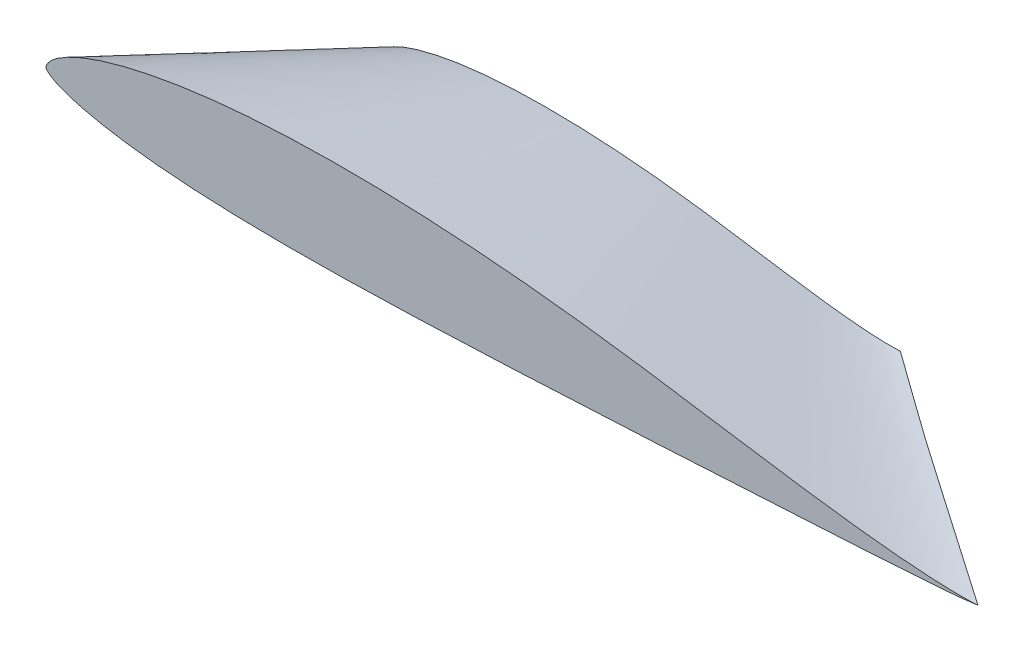
SolidWorks part; units mm, degrees
ref_plane "Front Plane" through (0, 0, 0) normal (0, 0, 1) x (1, 0, 0)
ref_plane "Top Plane" through (0, 0, 0) normal (0, 1, 0) x (1, 0, 0)
ref_plane "Right Plane" through (0, 0, 0) normal (1, 0, 0) x (0, 0, -1)
curve "Curve1"
  spline degree 3 poles (178.8235, -0.1536, 0) (180.3162, 0.0326, 0) (178.6769, -0.0979, 0) (177.3268, -0.1109, 0) (173.9976, -0.1057, 0) (169.9397, 0.1046, 0) (164.6882, 0.4858, 0) (158.5901, 1.1026, 0) (151.6988, 1.9482, 0) (144.1808, 2.9934, 0) (136.1635, 4.1927, 0) (127.7797, 5.4908, 0) (119.1442, 6.8173, 0) (110.3463, 8.0754, 0) (101.4587, 9.2, 0) (92.5465, 10.1562, 0) (83.6758, 10.9156, 0) (74.9166, 11.4682, 0) (66.342, 11.806, 0) (58.028, 11.9274, 0) (50.0487, 11.8319, 0) (42.4741, 11.515, 0) (35.367, 10.9819, 0) (28.7822, 10.24, 0) (22.7701, 9.3088, 0) (17.3773, 8.2269, 0) (12.6499, 7.0268, 0) (8.6305, 5.74, 0) (5.3502, 4.4039, 0) (2.8359, 3.0632, 0) (1.2518, 1.9009, 0) (0.4818, 1.0554, 0) (0.1891, 0.6046, 0) (0.0579, 0.3158, 0) (-0.0016, 0.0856, 0) (-0.0042, -0.0985, 0) (0.0738, -0.2696, 0) (0.2282, -0.4702, 0) (0.4808, -0.7088, 0) (0.9335, -1.0446, 0) (2.0075, -1.6855, 0) (4.0408, -2.5002, 0) (7.1529, -3.4084, 0) (11.097, -4.2605, 0) (15.8307, -5.0186, 0) (21.3187, -5.6503, 0) (27.5191, -6.1332, 0) (34.3853, -6.4628, 0) (41.8623, -6.6344, 0) (49.8874, -6.6565, 0) (58.3886, -6.5391, 0) (67.2847, -6.306, 0) (76.4836, -5.9763, 0) (85.8843, -5.5795, 0) (95.3777, -5.1338, 0) (104.8501, -4.6614, 0) (114.1865, -4.1746, 0) (123.2728, -3.6881, 0) (131.998, -3.2085, 0) (140.2557, -2.7461, 0) (147.9458, -2.3044, 0) (154.9716, -1.8945, 0) (161.2526, -1.5152, 0) (166.6878, -1.1747, 0) (171.2749, -0.8603, 0) (174.7811, -0.5984, 0) (177.6251, -0.3216, 0) (178.8235, -0.1536, 0) (180.3162, 0.0326, 0) (178.6769, -0.0979, 0) knots -0.013312 -0.00609 -0.00158 0 0.001669 0.006747 0.015187 0.026742 0.041155 0.058129 0.077283 0.098227 0.12058 0.143966 0.168018 0.192451 0.217075 0.24171 0.266182 0.29031 0.313903 0.336767 0.358704 0.37954 0.399122 0.417322 0.434037 0.449154 0.462553 0.474139 0.483848 0.491647 0.497539 0.499898 0.501005 0.501951 0.502492 0.502956 0.503431 0.504004 0.505035 0.506276 0.508636 0.515301 0.524213 0.535296 0.548467 0.563638 0.580726 0.599619 0.62018 0.642246 0.665633 0.690118 0.715452 0.741354 0.76752 0.793634 0.819375 0.844429 0.868488 0.891259 0.912467 0.93185 0.949165 0.964196 0.976755 0.986688 0.99391 0.99842 1 1.001669 1.006747 1.015187 periodic
ref_plane "Plane1" through (0, 0, -35) normal (0, 0, 1) x (1, 0, 0)
sketch "Sketch2" plane through (0, 0, 0) normal (0, 0, 1) x (1, 0, 0)
  line L0 (180, 0) -> (0, 0) construction
  spline S0 degree 3 poles (178.8235, -0.1536) (180.3162, 0.0326) (178.6769, -0.0979) (177.3268, -0.1109) (173.9976, -0.1057) (169.9397, 0.1046) (164.6882, 0.4858) (158.5901, 1.1026) (151.6988, 1.9482) (144.1808, 2.9934) (136.1635, 4.1927) (127.7797, 5.4908) (119.1442, 6.8173) (110.3463, 8.0754) (101.4587, 9.2) (92.5465, 10.1562) (83.6758, 10.9156) (74.9166, 11.4682) (66.342, 11.806) (58.028, 11.9274) (50.0487, 11.8319) (42.4741, 11.515) (35.367, 10.9819) (28.7822, 10.24) (22.7701, 9.3088) (17.3773, 8.2269) (12.6499, 7.0268) (8.6305, 5.74) (5.3502, 4.4039) (2.8359, 3.0632) (1.2518, 1.9009) (0.4818, 1.0554) (0.1891, 0.6046) (0.0579, 0.3158) (-0.0016, 0.0856) (-0.0042, -0.0985) (0.0738, -0.2696) (0.2282, -0.4702) (0.4808, -0.7088) (0.9335, -1.0446) (2.0075, -1.6855) (4.0408, -2.5002) (7.1529, -3.4084) (11.097, -4.2605) (15.8307, -5.0186) (21.3187, -5.6503) (27.5191, -6.1332) (34.3853, -6.4628) (41.8623, -6.6344) (49.8874, -6.6565) (58.3886, -6.5391) (67.2847, -6.306) (76.4836, -5.9763) (85.8843, -5.5795) (95.3777, -5.1338) (104.8501, -4.6614) (114.1865, -4.1746) (123.2728, -3.6881) (131.998, -3.2085) (140.2557, -2.7461) (147.9458, -2.3044) (154.9716, -1.8945) (161.2526, -1.5152) (166.6878, -1.1747) (171.2749, -0.8603) (174.7811, -0.5984) (177.6251, -0.3216) (178.8235, -0.1536) (180.3162, 0.0326) (178.6769, -0.0979) knots -0.013312 -0.00609 -0.00158 0 0.001669 0.006747 0.015187 0.026742 0.041155 0.058129 0.077283 0.098227 0.12058 0.143966 0.168018 0.192451 0.217075 0.24171 0.266182 0.29031 0.313903 0.336767 0.358704 0.37954 0.399122 0.417322 0.434037 0.449154 0.462553 0.474139 0.483848 0.491647 0.497539 0.499898 0.501005 0.501951 0.502492 0.502956 0.503431 0.504004 0.505035 0.506276 0.508636 0.515301 0.524213 0.535296 0.548467 0.563638 0.580726 0.599619 0.62018 0.642246 0.665633 0.690118 0.715452 0.741354 0.76752 0.793634 0.819375 0.844429 0.868488 0.891259 0.912467 0.93185 0.949165 0.964196 0.976755 0.986688 0.99391 0.99842 1 1.001669 1.006747 1.015187 only from (180, 0) to (180, 0) construction
  spline S1 degree 3 poles (178.8235, -0.1536) (180.3162, 0.0326) (178.6769, -0.0979) (177.3268, -0.1109) (173.9976, -0.1057) (169.9397, 0.1046) (164.6882, 0.4858) (158.5901, 1.1026) (151.6988, 1.9482) (144.1808, 2.9934) (136.1635, 4.1927) (127.7797, 5.4908) (119.1442, 6.8173) (110.3463, 8.0754) (101.4587, 9.2) (92.5465, 10.1562) (83.6758, 10.9156) (74.9166, 11.4682) (66.342, 11.806) (58.028, 11.9274) (50.0487, 11.8319) (42.4741, 11.515) (35.367, 10.9819) (28.7822, 10.24) (22.7701, 9.3088) (17.3773, 8.2269) (12.6499, 7.0268) (8.6305, 5.74) (5.3502, 4.4039) (2.8359, 3.0632) (1.2518, 1.9009) (0.4818, 1.0554) (0.1891, 0.6046) (0.0579, 0.3158) (-0.0016, 0.0856) (-0.0042, -0.0985) (0.0738, -0.2696) (0.2282, -0.4702) (0.4808, -0.7088) (0.9335, -1.0446) (2.0075, -1.6855) (4.0408, -2.5002) (7.1529, -3.4084) (11.097, -4.2605) (15.8307, -5.0186) (21.3187, -5.6503) (27.5191, -6.1332) (34.3853, -6.4628) (41.8623, -6.6344) (49.8874, -6.6565) (58.3886, -6.5391) (67.2847, -6.306) (76.4836, -5.9763) (85.8843, -5.5795) (95.3777, -5.1338) (104.8501, -4.6614) (114.1865, -4.1746) (123.2728, -3.6881) (131.998, -3.2085) (140.2557, -2.7461) (147.9458, -2.3044) (154.9716, -1.8945) (161.2526, -1.5152) (166.6878, -1.1747) (171.2749, -0.8603) (174.7811, -0.5984) (177.6251, -0.3216) (178.8235, -0.1536) (180.3162, 0.0326) (178.6769, -0.0979) knots -0.013312 -0.00609 -0.00158 0 0.001669 0.006747 0.015187 0.026742 0.041155 0.058129 0.077283 0.098227 0.12058 0.143966 0.168018 0.192451 0.217075 0.24171 0.266182 0.29031 0.313903 0.336767 0.358704 0.37954 0.399122 0.417322 0.434037 0.449154 0.462553 0.474139 0.483848 0.491647 0.497539 0.499898 0.501005 0.501951 0.502492 0.502956 0.503431 0.504004 0.505035 0.506276 0.508636 0.515301 0.524213 0.535296 0.548467 0.563638 0.580726 0.599619 0.62018 0.642246 0.665633 0.690118 0.715452 0.741354 0.76752 0.793634 0.819375 0.844429 0.868488 0.891259 0.912467 0.93185 0.949165 0.964196 0.976755 0.986688 0.99391 0.99842 1 1.001669 1.006747 1.015187 only from (180, 0) to (180, 0)
  point P4 (0, 0)
curve "Curve2"
  spline degree 3 poles (129.3464, -0.0853, 0) (130.1757, 0.0181, 0) (129.2649, -0.0544, 0) (128.5149, -0.0616, 0) (126.6653, -0.0587, 0) (124.4109, 0.0581, 0) (121.4935, 0.2699, 0) (118.1056, 0.6125, 0) (114.2771, 1.0823, 0) (110.1004, 1.663, 0) (105.6464, 2.3293, 0) (100.9887, 3.0504, 0) (96.1912, 3.7874, 0) (91.3035, 4.4863, 0) (86.366, 5.1111, 0) (81.4147, 5.6423, 0) (76.4865, 6.0642, 0) (71.6203, 6.3712, 0) (66.8567, 6.5589, 0) (62.2378, 6.6263, 0) (57.8048, 6.5733, 0) (53.5967, 6.3972, 0) (49.6483, 6.1011, 0) (45.9901, 5.6889, 0) (42.65, 5.1716, 0) (39.654, 4.5705, 0) (37.0277, 3.9038, 0) (34.7947, 3.1889, 0) (32.9723, 2.4466, 0) (31.5755, 1.7018, 0) (30.6954, 1.0561, 0) (30.2677, 0.5864, 0) (30.1051, 0.3359, 0) (30.0322, 0.1755, 0) (29.9991, 0.0476, 0) (29.9977, -0.0547, 0) (30.041, -0.1498, 0) (30.1268, -0.2612, 0) (30.2671, -0.3938, 0) (30.5186, -0.5803, 0) (31.1153, -0.9364, 0) (32.2449, -1.389, 0) (33.9738, -1.8935, 0) (36.165, -2.3669, 0) (38.7949, -2.7881, 0) (41.8437, -3.1391, 0) (45.2884, -3.4073, 0) (49.1029, -3.5905, 0) (53.2568, -3.6858, 0) (57.7152, -3.6981, 0) (62.4381, -3.6328, 0) (67.3804, -3.5033, 0) (72.4909, -3.3202, 0) (77.7135, -3.0997, 0) (82.9876, -2.8521, 0) (88.2501, -2.5897, 0) (93.437, -2.3192, 0) (98.4849, -2.0489, 0) (103.3322, -1.7825, 0) (107.9198, -1.5256, 0) (112.1921, -1.2802, 0) (116.0954, -1.0525, 0) (119.5848, -0.8418, 0) (122.6043, -0.6526, 0) (125.1527, -0.4779, 0) (127.1006, -0.3325, 0) (128.6806, -0.1786, 0) (129.3464, -0.0853, 0) (130.1757, 0.0181, 0) (129.2649, -0.0544, 0) knots -0.013312 -0.00609 -0.00158 0 0.001669 0.006747 0.015187 0.026742 0.041155 0.058129 0.077283 0.098227 0.12058 0.143966 0.168018 0.192451 0.217075 0.24171 0.266182 0.29031 0.313903 0.336767 0.358704 0.37954 0.399122 0.417322 0.434037 0.449154 0.462553 0.474139 0.483848 0.491647 0.497539 0.499898 0.501005 0.501951 0.502492 0.502956 0.503431 0.504004 0.505035 0.506276 0.508636 0.515301 0.524213 0.535296 0.548467 0.563638 0.580726 0.599619 0.62018 0.642246 0.665633 0.690118 0.715452 0.741354 0.76752 0.793634 0.819375 0.844429 0.868488 0.891259 0.912467 0.93185 0.949165 0.964196 0.976755 0.986688 0.99391 0.99842 1 1.001669 1.006747 1.015187 periodic
sketch "Sketch3" plane through (0, 0, -35) normal (0, 0, 1) x (1, 0, 0)
  line L0 (130, 0) -> (29.9996, 0) construction
  spline S0 degree 3 poles (129.3464, -0.0853) (130.1757, 0.0181) (129.2649, -0.0544) (128.5149, -0.0616) (126.6653, -0.0587) (124.4109, 0.0581) (121.4935, 0.2699) (118.1056, 0.6125) (114.2771, 1.0823) (110.1004, 1.663) (105.6464, 2.3293) (100.9887, 3.0504) (96.1912, 3.7874) (91.3035, 4.4863) (86.366, 5.1111) (81.4147, 5.6423) (76.4865, 6.0642) (71.6203, 6.3712) (66.8567, 6.5589) (62.2378, 6.6263) (57.8048, 6.5733) (53.5967, 6.3972) (49.6483, 6.1011) (45.9901, 5.6889) (42.65, 5.1716) (39.654, 4.5705) (37.0277, 3.9038) (34.7947, 3.1889) (32.9723, 2.4466) (31.5755, 1.7018) (30.6954, 1.0561) (30.2677, 0.5864) (30.1051, 0.3359) (30.0322, 0.1755) (29.9991, 0.0476) (29.9977, -0.0547) (30.041, -0.1498) (30.1268, -0.2612) (30.2671, -0.3938) (30.5186, -0.5803) (31.1153, -0.9364) (32.2449, -1.389) (33.9738, -1.8935) (36.165, -2.3669) (38.7949, -2.7881) (41.8437, -3.1391) (45.2884, -3.4073) (49.1029, -3.5905) (53.2568, -3.6858) (57.7152, -3.6981) (62.4381, -3.6328) (67.3804, -3.5033) (72.4909, -3.3202) (77.7135, -3.0997) (82.9876, -2.8521) (88.2501, -2.5897) (93.437, -2.3192) (98.4849, -2.0489) (103.3322, -1.7825) (107.9198, -1.5256) (112.1921, -1.2802) (116.0954, -1.0525) (119.5848, -0.8418) (122.6043, -0.6526) (125.1527, -0.4779) (127.1006, -0.3325) (128.6806, -0.1786) (129.3464, -0.0853) (130.1757, 0.0181) (129.2649, -0.0544) knots -0.013312 -0.00609 -0.00158 0 0.001669 0.006747 0.015187 0.026742 0.041155 0.058129 0.077283 0.098227 0.12058 0.143966 0.168018 0.192451 0.217075 0.24171 0.266182 0.29031 0.313903 0.336767 0.358704 0.37954 0.399122 0.417322 0.434037 0.449154 0.462553 0.474139 0.483848 0.491647 0.497539 0.499898 0.501005 0.501951 0.502492 0.502956 0.503431 0.504004 0.505035 0.506276 0.508636 0.515301 0.524213 0.535296 0.548467 0.563638 0.580726 0.599619 0.62018 0.642246 0.665633 0.690118 0.715452 0.741354 0.76752 0.793634 0.819375 0.844429 0.868488 0.891259 0.912467 0.93185 0.949165 0.964196 0.976755 0.986688 0.99391 0.99842 1 1.001669 1.006747 1.015187 only from (130, 0) to (130, 0) construction
  spline S1 degree 3 poles (129.3464, -0.0853) (130.1757, 0.0181) (129.2649, -0.0544) (128.5149, -0.0616) (126.6653, -0.0587) (124.4109, 0.0581) (121.4935, 0.2699) (118.1056, 0.6125) (114.2771, 1.0823) (110.1004, 1.663) (105.6464, 2.3293) (100.9887, 3.0504) (96.1912, 3.7874) (91.3035, 4.4863) (86.366, 5.1111) (81.4147, 5.6423) (76.4865, 6.0642) (71.6203, 6.3712) (66.8567, 6.5589) (62.2378, 6.6263) (57.8048, 6.5733) (53.5967, 6.3972) (49.6483, 6.1011) (45.9901, 5.6889) (42.65, 5.1716) (39.654, 4.5705) (37.0277, 3.9038) (34.7947, 3.1889) (32.9723, 2.4466) (31.5755, 1.7018) (30.6954, 1.0561) (30.2677, 0.5864) (30.1051, 0.3359) (30.0322, 0.1755) (29.9991, 0.0476) (29.9977, -0.0547) (30.041, -0.1498) (30.1268, -0.2612) (30.2671, -0.3938) (30.5186, -0.5803) (31.1153, -0.9364) (32.2449, -1.389) (33.9738, -1.8935) (36.165, -2.3669) (38.7949, -2.7881) (41.8437, -3.1391) (45.2884, -3.4073) (49.1029, -3.5905) (53.2568, -3.6858) (57.7152, -3.6981) (62.4381, -3.6328) (67.3804, -3.5033) (72.4909, -3.3202) (77.7135, -3.0997) (82.9876, -2.8521) (88.2501, -2.5897) (93.437, -2.3192) (98.4849, -2.0489) (103.3322, -1.7825) (107.9198, -1.5256) (112.1921, -1.2802) (116.0954, -1.0525) (119.5848, -0.8418) (122.6043, -0.6526) (125.1527, -0.4779) (127.1006, -0.3325) (128.6806, -0.1786) (129.3464, -0.0853) (130.1757, 0.0181) (129.2649, -0.0544) knots -0.013312 -0.00609 -0.00158 0 0.001669 0.006747 0.015187 0.026742 0.041155 0.058129 0.077283 0.098227 0.12058 0.143966 0.168018 0.192451 0.217075 0.24171 0.266182 0.29031 0.313903 0.336767 0.358704 0.37954 0.399122 0.417322 0.434037 0.449154 0.462553 0.474139 0.483848 0.491647 0.497539 0.499898 0.501005 0.501951 0.502492 0.502956 0.503431 0.504004 0.505035 0.506276 0.508636 0.515301 0.524213 0.535296 0.548467 0.563638 0.580726 0.599619 0.62018 0.642246 0.665633 0.690118 0.715452 0.741354 0.76752 0.793634 0.819375 0.844429 0.868488 0.891259 0.912467 0.93185 0.949165 0.964196 0.976755 0.986688 0.99391 0.99842 1 1.001669 1.006747 1.015187 only from (130, 0) to (130, 0)
loft "Loft1" add profiles "Sketch2", "Sketch3" connector at (55.3868, 11.8834, 0) connector at (61.3985, 6.6053, -35)
mirror "Mirror1" [suppressed] about plane through (0, 0, 0) normal (0, 0, 1)
ref_axis "Axis4" through (0, 0, -61.6271) along (0, 0, 1)
ref_axis "Axis1" through (180, 0, 0) along (-1, 0, 0)
ref_axis "Axis2" through (130, 0, -35) along (-1, 0, 0)
ref_point "Point1"
ref_axis "Axis3" through (-0.0007, 0, 0) along (0.6508, 0, -0.7593)
sketch "Sketch4" plane through (0, 0, 0) normal (0, 1, 0) x (1, 0, 0)
  line L0 (0, 0) -> (141.8779, 107.8393) construction
  line L1 (0, 0) -> (100, 360) construction
  line L3 (25.3509, 91.2632) -> (60.0348, 45.6316) construction
  line L4 (94.7187, 0) -> (60.0348, 45.6316) construction
  line L5 (180, 0) -> (0, 0) construction
  point P5 (48.5919, 74.9411)
  point P9 (99.8417, 190.0458)
  dimension "D1" = 360
  dimension "D2" = 100
ref_plane "Plane2" through (0, 0, 0) normal (0.6051, 0, 0.7961) x (0.7961, 0, -0.6051)
sketch "Sketch5" plane through (0, 0, 0) normal (0.6051, 0, 0.7961) x (0.7961, 0, -0.6051)
  line L0 (56.2192, -31.5843) -> (68.1479, 36.0669) construction
  line L1 (56.2192, -31.5843) -> (56.2192, 24.9899) construction
  dimension "D1" = 10
ref_axis "Axis5" through (44.7577, -31.5843, -34.0197) along (0.1382, 0.9848, -0.1051)
ref_point "Point2"
